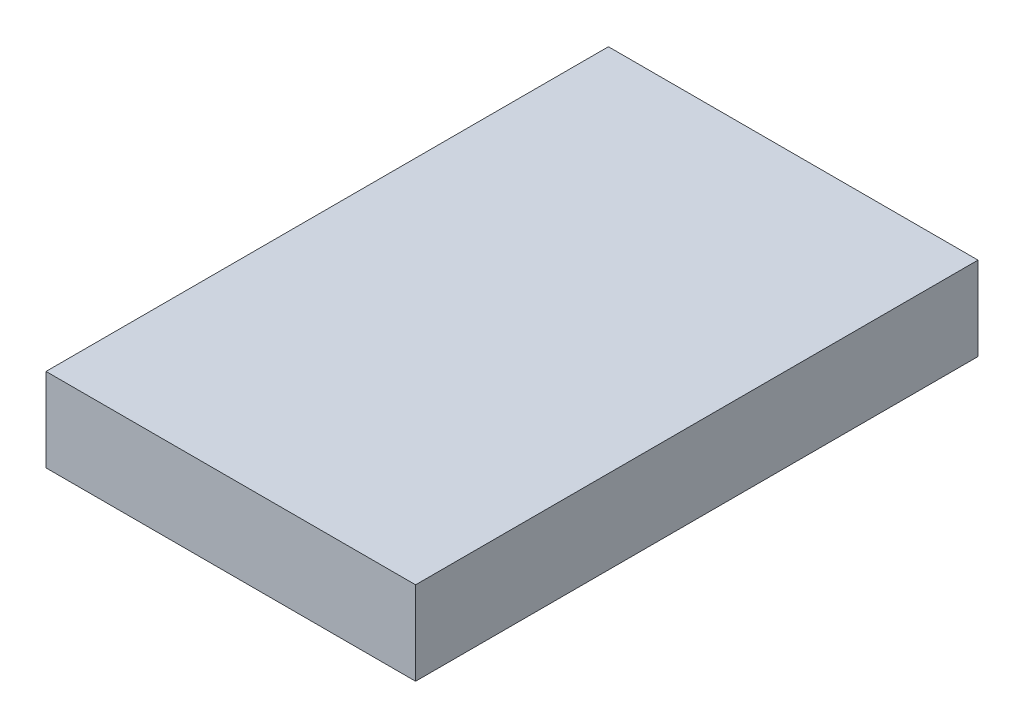
SolidWorks part; units mm, degrees
material "PBTP"
ref_plane "Front Plane" through (0, 0, 0) normal (0, 0, 1) x (1, 0, 0)
ref_plane "Top Plane" through (0, 0, 0) normal (0, 1, 0) x (1, 0, 0)
ref_plane "Right Plane" through (0, 0, 0) normal (1, 0, 0) x (0, 0, -1)
sketch "Sketch1" plane through (0, 0, 0) normal (0, 1, 0) x (1, 0, 0)
  line L1 (-11.5, -17.5) -> (11.5, -17.5)
  line L2 (-11.5, -17.5) -> (-11.5, 17.5)
  line L3 (-11.5, 17.5) -> (11.5, 17.5)
  line L4 (11.5, -17.5) -> (11.5, 17.5)
  line L5 (-11.5, -17.5) -> (11.5, 17.5) construction
  line L6 (-11.5, 17.5) -> (11.5, -17.5) construction
  point P0 (0, 0)
  dimension "D1" = 23
  dimension "D2" = 35
extrude "Boss-Extrude1" add sketch "Sketch1" along normal blind 5.2
